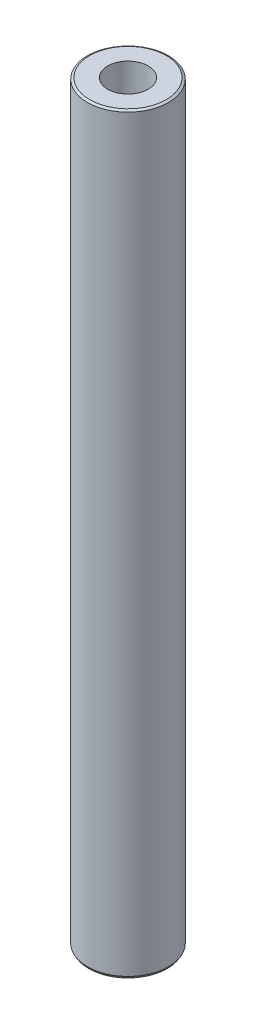
SolidWorks part; units mm, degrees
ref_plane "Front Plane" through (0, 0, 0) normal (0, 0, 1) x (1, 0, 0)
ref_plane "Top Plane" through (0, 0, 0) normal (0, 1, 0) x (1, 0, 0)
ref_plane "Right Plane" through (0, 0, 0) normal (1, 0, 0) x (0, 0, -1)
sketch "Sketch1" plane through (0, 0, 0) normal (0, 1, 0) x (1, 0, 0)
  circle A0 centre (0, 0) radius 12.5
  dimension "SHAFT_OD" = 25
extrude "Boss-Extrude1" add sketch "Sketch1" along normal blind 231.9402
sketch "Sketch2" plane through (0, 0, 0) normal (0, 1, 0) x (1, 0, 0)
  circle A0 centre (0, 0) radius 6.2387
  dimension "BORE_D" = 12.4774
extrude "Cut-Extrude1" cut sketch "Sketch2" along normal through all
chamfer "Chamfer1" distance 0.4058 angle 60 2 edges at (0, 231.9402, 12.5) (0, 0, 12.5) first distance on face at (0, 231.9402, 12.5) first distance on face at (0, 0, 6.2387)
